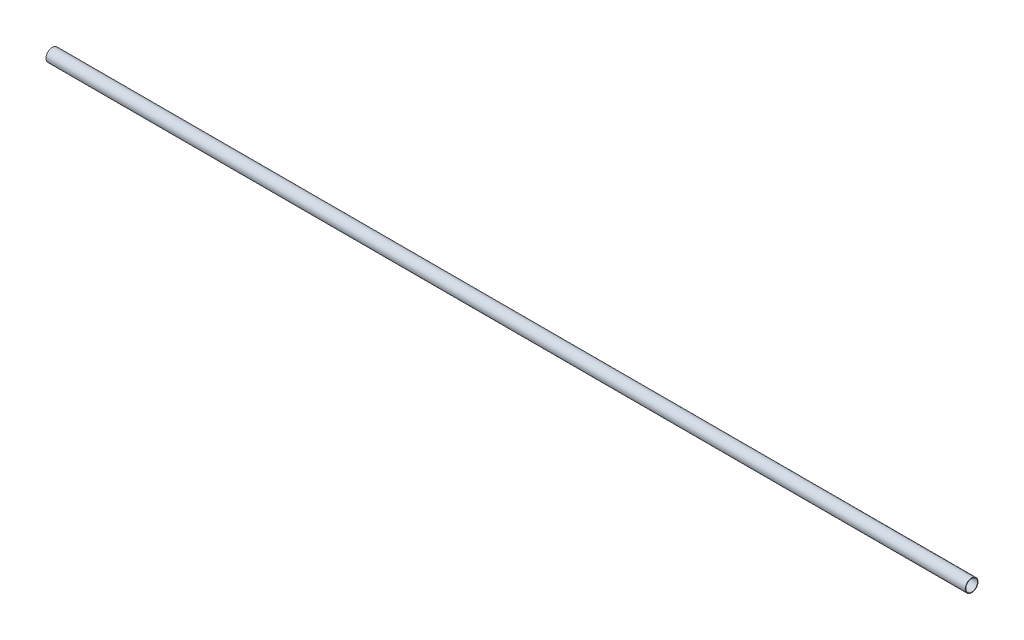
SolidWorks part; units mm, degrees
ref_plane "Front" through (0, 0, 0) normal (0, 0, 1) x (1, 0, 0)
ref_plane "Top" through (0, 0, 0) normal (0, 1, 0) x (1, 0, 0)
ref_plane "Right" through (0, 0, 0) normal (1, 0, 0) x (0, 0, -1)
sketch "Sketch1" plane through (0, 0, 0) normal (1, 0, 0) x (0, 0, -1)
  circle A0 centre (0, 0) radius 6.35
  circle A1 centre (0, 0) radius 5.842
  point P4 (6.35, 0)
  point P5 (5.842, 0)
  dimension "OD" = 12.7
  dimension "ID" = 11.684
  dimension "Wall" = 0.508
extrude "Extrude1" add sketch "Sketch1" along normal mid plane 914.4
sketch "Sketch2" plane through (0, 0, 0) normal (0, 0, 1) x (1, 0, 0)
  line L0 (-457.2, 0) -> (457.2, 0) construction
  line L1 (-457.2, 6.35) -> (-457.2, -6.35) construction
sketch "Sketch3" plane through (-457.2, 0, 0) normal (-1, 0, 0) x (0, 0, 1)
  circle A0 centre (0, 0) radius 6.35
